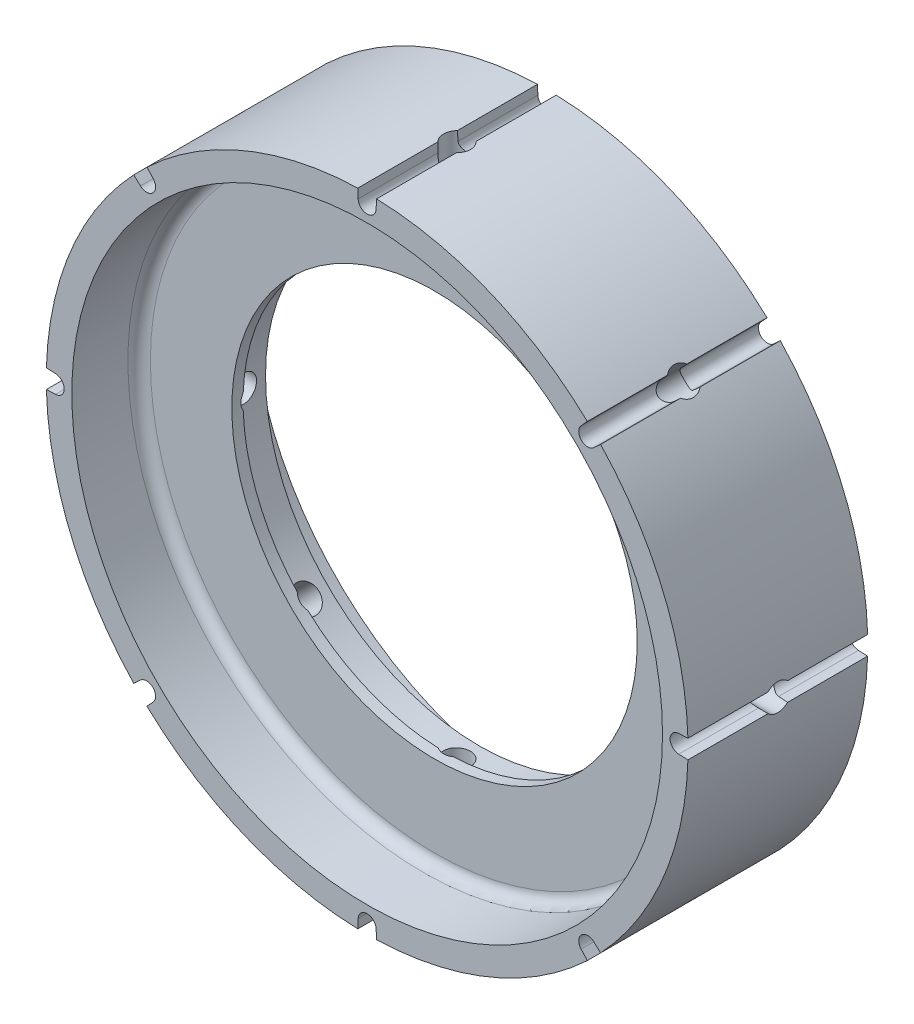
SolidWorks part; units mm, degrees
ref_plane "Front Plane" through (0, 0, 0) normal (0, 0, 1) x (1, 0, 0)
ref_plane "Top Plane" through (0, 0, 0) normal (0, 1, 0) x (1, 0, 0)
ref_plane "Right Plane" through (0, 0, 0) normal (1, 0, 0) x (0, 0, -1)
sketch "Sketch1" plane through (0, 0, 0) normal (0, 0, 1) x (1, 0, 0)
  circle A4 centre (0, 0) radius 14.2875
  circle A5 centre (0, 0) radius 13.15
  circle A6 centre (0, 0) radius 13.15
  dimension "D1" = 0.15
  dimension "D3" = 1.1375
  dimension "D2" = 28.575
extrude "Boss-Extrude1" add sketch "Sketch1" against normal blind 3
sketch "Sketch2" plane through (0, 0, 0) normal (0, 0, 1) x (1, 0, 0)
  circle A0 centre (0, 0) radius 14.2875
  circle A1 centre (0, 0) radius 9.025
  circle A2 centre (0, 0) radius 14.2875 construction
  dimension "D1" = 18.05
extrude "Boss-Extrude2" add sketch "Sketch2" along normal blind 2
sketch "Sketch3" plane through (0, 0, 2) normal (0, 0, 1) x (1, 0, 0)
  circle A0 centre (0, 0) radius 13.15 construction
  circle A1 centre (0, 0) radius 14.2875
  circle A2 centre (0, 0) radius 14.2875
  circle A3 centre (0, 0) radius 13.15
  dimension "D1" = 0
extrude "Boss-Extrude3" add sketch "Sketch3" along normal blind 3
fillet "Fillet1" radius 0.5 2 edges at (13.15, 0, 2) (13.15, 0, 0)
sketch "Sketch4" plane through (0, 0, 0) normal (0, 0, -1) x (-1, 0, 0)
  circle A1 centre (0, 0) radius 9.525
extrude "Cut-Extrude2" cut sketch "Sketch4" against normal blind 1.5
sketch "Sketch5" plane through (0, 0, -3) normal (0, 0, -1) x (-1, 0, 0)
  line L0 (-13.8709, 0.3997) -> (-14.2814, 0.4167)
  line L1 (-13.8709, -0.3997) -> (-14.2814, -0.4167)
  circle A3 centre (0, 0) radius 14.2875 construction
  circle A5 centre (0, 0) radius 14.2875
  circle A6 centre (-13.8875, 0) radius 0.4
  circle M4 centre (0, 0) radius 14.2875
extrude "Cut-Extrude4" cut sketch "Sketch5" against normal through all contours A6 | A6 L0 M4 | A6 A5 L1 region at (14.1918, 0.3195, -3) region at (13.8875, 0, -3) region at (14.1918, -0.3195, -3)
ref_plane "Plane1" through (14.2814, 0, 0) normal (1, 0, 0) x (0, 0, -1)
sketch "Sketch6" plane through (14.2814, 0, 0) normal (1, 0, 0) x (0, 0, -1)
  line L0 (-5, 0.4167) -> (3, 0.4167) construction
  line L1 (-5, 0.4167) -> (3, 0.4167)
  circle A0 centre (-1, 0) radius 0.6
extrude "Cut-Extrude5" cut sketch "Sketch6" against normal blind 10 contours L1 A0 | L1 A0 region at (14.2814, 0.4911, 1) region at (14.2814, -0.0525, 1)
sketch "Sketch7" plane through (0, 0, 0) normal (0, 1, 0) x (1, 0, 0)
  line L0 (0, 0) -> (0, 6.608) construction
pattern_circular "CirPattern1" count 8 over 360 about axis through (0, 0, 0) along (0, 0, -1) of "Cut-Extrude5", "Cut-Extrude4"
